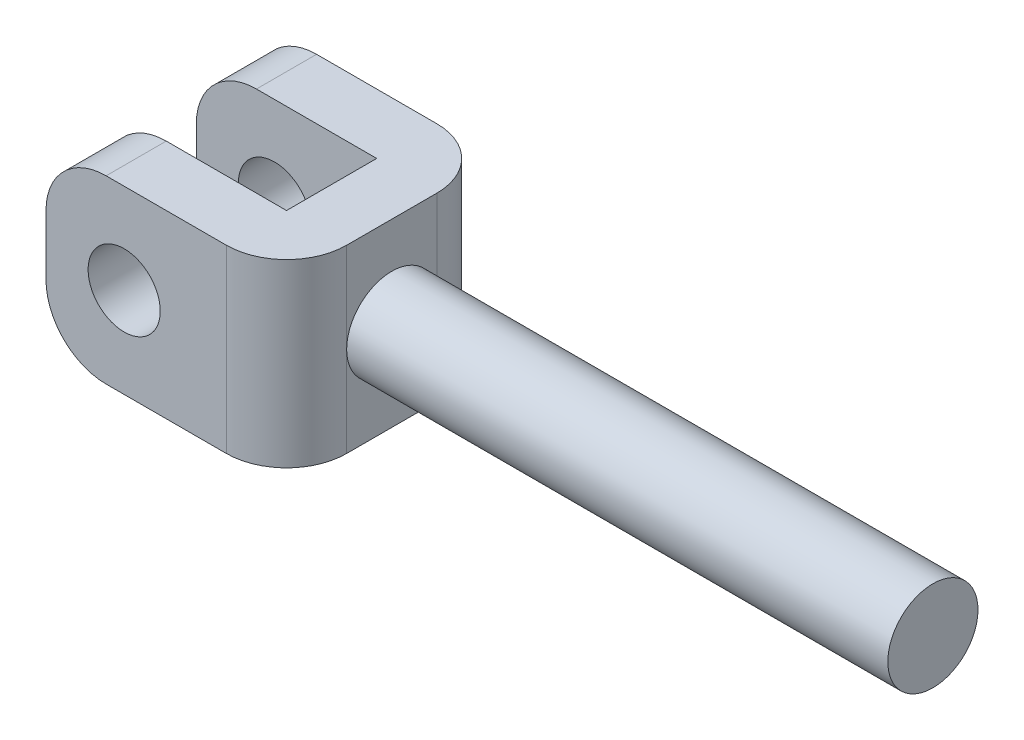
SolidWorks part; units mm, degrees
ref_plane "Front Plane" through (0, 0, 0) normal (0, 0, 1) x (1, 0, 0)
ref_plane "Top Plane" through (0, 0, 0) normal (0, 1, 0) x (1, 0, 0)
ref_plane "Right Plane" through (0, 0, 0) normal (1, 0, 0) x (0, 0, -1)
sketch "Sketch1" plane through (0, 0, 0) normal (1, 0, 0) x (0, 0, -1)
  circle A0 centre (0, 0) radius 0.75
  dimension "D1" = 1.5
extrude "Boss-Extrude1" add sketch "Sketch1" along normal blind 10
sketch "Sketch2" plane through (0, 0, 0) normal (0, 1, 0) x (1, 0, 0)
  line L0 (1, 1.75) -> (1, -1.75)
  line L2 (0, 0.75) -> (0, -0.75)
  line L5 (1, -1.75) -> (-3, -1.75)
  line L6 (-3, 1.75) -> (-3, 0.75)
  line L7 (1, 1.75) -> (-3, 1.75)
  line L8 (0, 0.75) -> (-3, 0.75)
  line L10 (-3, -0.75) -> (0, -0.75)
  line L11 (-3, -0.75) -> (-3, -1.75)
  line L13 (-3, 1.75) -> (-3, -1.75) construction
  line L14 (-2, 0.75) -> (-2, -0.75) construction
  line L15 (0, 0.75) -> (-2, 0.75) construction
  line L16 (0, -0.75) -> (-2, -0.75) construction
  dimension "D1" = 4
  dimension "D2" = 1
extrude "Boss-Extrude2" add sketch "Sketch2" along normal blind 1.5 and the other way blind 1.5
fillet "Fillet1" radius 1 6 edges at (-3, 1.5, -1.25) (-3, -1.5, -1.25) (-3, -1.5, 1.25) (-3, 1.5, 1.25) (1, 0, -1.75) (1, 0, 1.75)
sketch "Sketch3" plane through (0, 0, -1.75) normal (0, 0, -1) x (-1, 0, 0)
  line L0 (0, -1.5) -> (2, -1.5) construction
  line L2 (0, 1.5) -> (0, -1.5) construction
  circle A0 centre (1.7, 0) radius 0.6
  dimension "D1" = 1.2
  dimension "D2" = 1.5
  dimension "D3" = 1.7
extrude "Cut-Extrude1" cut sketch "Sketch3" against normal blind 5
